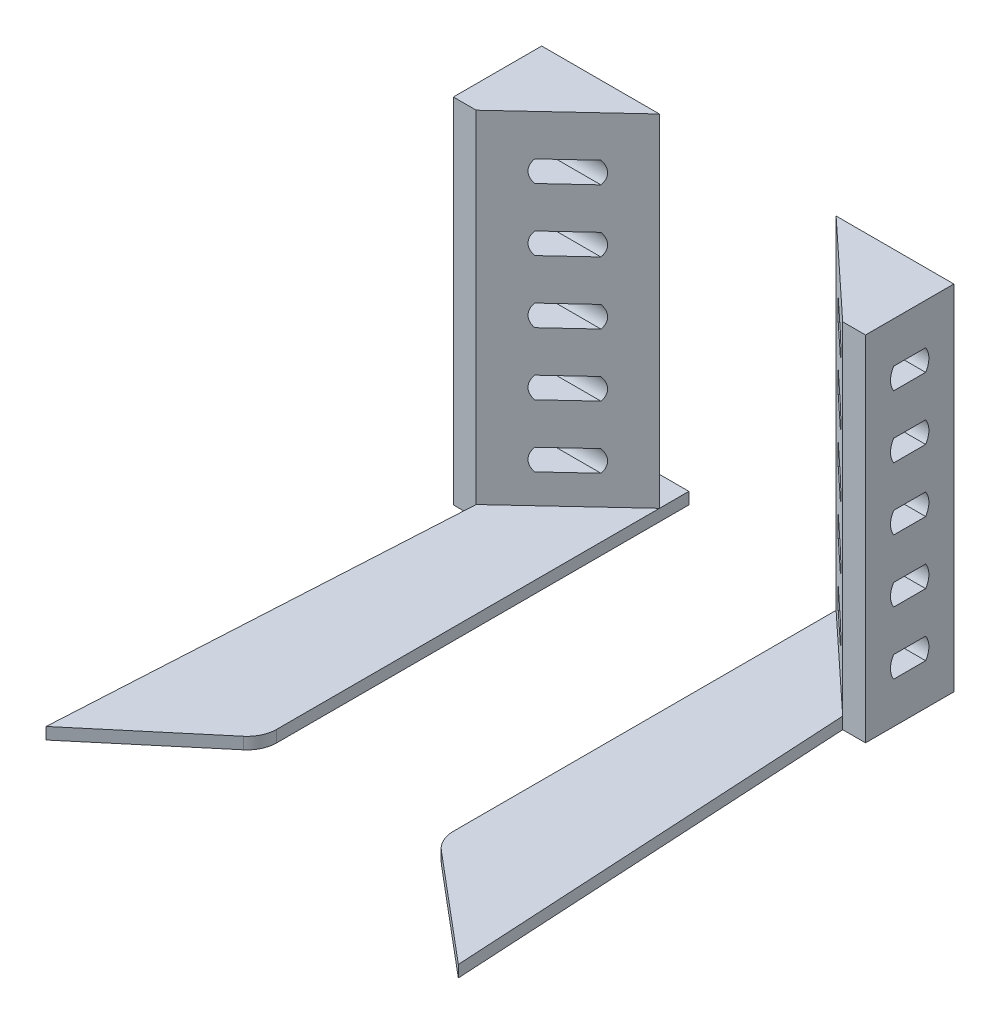
SolidWorks part; units mm, degrees
ref_plane "Front Plane" through (0, 0, 0) normal (0, 0, 1) x (1, 0, 0)
ref_plane "Top Plane" through (0, 0, 0) normal (0, 1, 0) x (1, 0, 0)
ref_plane "Right Plane" through (0, 0, 0) normal (1, 0, 0) x (0, 0, -1)
sketch "Sketch1" plane through (0, 0, 0) normal (0, 1, 0) x (1, 0, 0)
  line L0 (0, 0) -> (0, 13.4699) construction
  line L1 (0, 0) -> (3.6856, 0) construction
  line L2 (1.7808, -38.8258) -> (20, -54.1561)
  line L3 (0, 35) -> (15, 35)
  line L4 (0, 35) -> (0, -35)
  line L7 (15, 35) -> (20, -54.1561)
  line L8 (20, -54.1561) -> (20, 20.5292) construction
  line L9 (0, 30) -> (16.1216, 15)
  line L10 (20, 30) -> (0, 30)
  line L11 (20, 30) -> (20, 15)
  line L14 (16.1216, 15) -> (20, 15)
  line L15 (-15, 0) -> (-15, 85.0189) construction
  line L17 (-50, -54.1561) -> (-50, 20.5292) construction
  line L18 (-30, 0) -> (-33.6856, 0) construction
  line L19 (-30, 0) -> (-30, 13.4699) construction
  line L20 (-46.1216, 15) -> (-50, 15)
  line L21 (-50, 30) -> (-50, 15)
  line L22 (-50, 30) -> (-30, 30)
  line L23 (-30, 30) -> (-46.1216, 15)
  line L24 (-45, 35) -> (-50, -54.1561)
  line L25 (-30, 35) -> (-30, -35)
  line L26 (-30, 35) -> (-45, 35)
  line L27 (-31.7808, -38.8258) -> (-50, -54.1561)
  arc A0 (0, -35) -> (1.7808, -38.8258) centre (5, -35) ccw
  arc A1 (-30, -35) -> (-31.7808, -38.8258) centre (-35, -35) cw
  point P2 (0, 0)
  point P40 (0, 0)
  dimension "D1" = 5
  dimension "D2" = 20
  dimension "D3" = 15
  dimension "D4" = 70
  dimension "D5" = 46.712
  dimension "D6" = 15
  dimension "D7" = 5
  dimension "D8" = 15
extrude "Boss-Extrude1" add sketch "Sketch1" along normal blind 2 contours L10 L7 L3 L4 | L7 L10 L4 | L4 A0 L2 L7 | L11 L10 L7 region at (9.035, 0, 12.8099) region at (10.4673, 0, -25) region at (17.8437, 0, -22.7446) region at (7.5703, 0, -32.4923)
extrude "Boss-Extrude3" add sketch "Sketch1<5>" along normal blind 60 contours L7 L10 L9 | L7 L14 L11 L10 region at (10.4673, 0, -25) region at (17.8437, 0, -22.7446)
sketch "Sketch1<5>" plane through (0, 0, 0) normal (0, 1, 0) x (1, 0, 0) same geometry as "Sketch1"
sketch "Sketch4" plane through (20, 0, 0) normal (1, 0, 0) x (0, 0, -1)
  line L0 (30, 60) -> (15, 60) construction
  line L1 (19.79, 53.0167) -> (25.21, 53.0167)
  line L2 (19.2411, 51.2067) -> (25.7589, 51.2067) construction
  line L3 (19.79, 49.3967) -> (25.21, 49.3967)
  line L4 (22.5, 53.0167) -> (22.5, 49.3967) construction
  line L6 (19.79, 42.4133) -> (25.21, 42.4133)
  line L7 (19.2411, 40.6033) -> (25.7589, 40.6033) construction
  line L8 (19.79, 38.7933) -> (25.21, 38.7933)
  line L9 (22.5, 42.4133) -> (22.5, 38.7933) construction
  line L10 (19.79, 31.81) -> (25.21, 31.81)
  line L11 (19.2411, 30) -> (25.7589, 30) construction
  line L12 (19.79, 28.19) -> (25.21, 28.19)
  line L13 (22.5, 31.81) -> (22.5, 28.19) construction
  line L14 (19.79, 21.2067) -> (25.21, 21.2067)
  line L15 (19.2411, 19.3967) -> (25.7589, 19.3967) construction
  line L16 (19.79, 17.5867) -> (25.21, 17.5867)
  line L17 (22.5, 21.2067) -> (22.5, 17.5867) construction
  line L18 (19.79, 10.6033) -> (25.21, 10.6033)
  line L19 (19.2411, 8.7933) -> (25.7589, 8.7933) construction
  line L20 (19.79, 6.9833) -> (25.21, 6.9833)
  line L21 (22.5, 10.6033) -> (22.5, 6.9833) construction
  line L22 (22.5, 60) -> (22.5, 53.0167) construction
  line L23 (22.5, 49.3967) -> (22.5, 42.4133) construction
  line L24 (22.5, 38.7933) -> (22.5, 31.81) construction
  line L25 (22.5, 28.19) -> (22.5, 21.2067) construction
  line L26 (22.5, 17.5867) -> (22.5, 10.6033) construction
  line L27 (22.5, 6.9833) -> (22.5, 0) construction
  line L28 (30, 0) -> (15, 0) construction
  circle A0 centre (22.5, 51.2067) radius 3.2589 construction
  arc A1 (19.79, 53.0167) -> (19.79, 49.3967) centre (22.5, 51.2067) ccw
  arc A2 (25.21, 53.0167) -> (25.21, 49.3967) centre (22.5, 51.2067) cw
  circle A3 centre (22.5, 40.6033) radius 3.2589 construction
  arc A4 (19.79, 42.4133) -> (19.79, 38.7933) centre (22.5, 40.6033) ccw
  arc A5 (25.21, 42.4133) -> (25.21, 38.7933) centre (22.5, 40.6033) cw
  circle A6 centre (22.5, 30) radius 3.2589 construction
  arc A7 (19.79, 31.81) -> (19.79, 28.19) centre (22.5, 30) ccw
  arc A8 (25.21, 31.81) -> (25.21, 28.19) centre (22.5, 30) cw
  circle A9 centre (22.5, 19.3967) radius 3.2589 construction
  arc A10 (19.79, 21.2067) -> (19.79, 17.5867) centre (22.5, 19.3967) ccw
  arc A11 (25.21, 21.2067) -> (25.21, 17.5867) centre (22.5, 19.3967) cw
  circle A12 centre (22.5, 8.7933) radius 3.2589 construction
  arc A13 (19.79, 10.6033) -> (19.79, 6.9833) centre (22.5, 8.7933) ccw
  arc A14 (25.21, 10.6033) -> (25.21, 6.9833) centre (22.5, 8.7933) cw
  point P4 (22.5, 60)
  dimension "D1" = 5.42
  dimension "D2" = 3.62
extrude "Cut-Extrude1" cut sketch "Sketch4" against normal through all both and the other way through all
extrude "Boss-Extrude5" add sketch "Sketch1<9>" along normal blind 2 separate body contours A1 L25 L23 L24 L27 | L24 L22 L21 L20 | L22 L24 L23 | L25 L26 L24 L22 region at (-40.4673, 0, -25) region at (-39.035, 0, 12.8099) region at (-47.8437, 0, -22.7446) region at (-37.5703, 0, -32.4923)
sketch "Sketch1<9>" plane through (0, 0, 0) normal (0, 1, 0) x (1, 0, 0) same geometry as "Sketch1"
extrude "Boss-Extrude6" add sketch "Sketch1<10>" along normal blind 60 contours L22 L24 L23 | L24 L22 L21 L20 region at (-40.4673, 0, -25) region at (-47.8437, 0, -22.7446)
sketch "Sketch1<10>" plane through (0, 0, 0) normal (0, 1, 0) x (1, 0, 0) same geometry as "Sketch1"
sketch "Sketch7" plane through (-50, 0, 0) normal (-1, 0, 0) x (0, 0, 1)
  line L0 (-25.21, 53.0167) -> (-19.79, 53.0167)
  line L1 (-25.7589, 51.2067) -> (-19.2411, 51.2067) construction
  line L2 (-25.21, 49.3967) -> (-19.79, 49.3967)
  line L3 (-22.5, 53.0167) -> (-22.5, 49.3967) construction
  line L4 (-25.21, 42.4133) -> (-19.79, 42.4133)
  line L5 (-25.7589, 40.6033) -> (-19.2411, 40.6033) construction
  line L6 (-25.21, 38.7933) -> (-19.79, 38.7933)
  line L7 (-22.5, 42.4133) -> (-22.5, 38.7933) construction
  line L8 (-25.21, 31.81) -> (-19.79, 31.81)
  line L9 (-25.7589, 30) -> (-19.2411, 30) construction
  line L10 (-25.21, 28.19) -> (-19.79, 28.19)
  line L11 (-22.5, 31.81) -> (-22.5, 28.19) construction
  line L12 (-25.21, 21.2067) -> (-19.79, 21.2067)
  line L13 (-25.7589, 19.3967) -> (-19.2411, 19.3967) construction
  line L14 (-25.21, 17.5867) -> (-19.79, 17.5867)
  line L15 (-22.5, 21.2067) -> (-22.5, 17.5867) construction
  line L16 (-25.21, 10.6033) -> (-19.79, 10.6033)
  line L17 (-25.7589, 8.7933) -> (-19.2411, 8.7933) construction
  line L18 (-25.21, 6.9833) -> (-19.79, 6.9833)
  line L19 (-22.5, 10.6033) -> (-22.5, 6.9833) construction
  line L20 (-22.5, 60) -> (-22.5, 53.0167) construction
  line L21 (-22.5, 49.3967) -> (-22.5, 42.4133) construction
  line L22 (-22.5, 38.7933) -> (-22.5, 31.81) construction
  line L23 (-22.5, 28.19) -> (-22.5, 21.2067) construction
  line L24 (-22.5, 17.5867) -> (-22.5, 10.6033) construction
  line L25 (-22.5, 6.9833) -> (-22.5, 0) construction
  line L26 (-30, 0) -> (-15, 0) construction
  line L27 (-30, 60) -> (-15, 60) construction
  circle A0 centre (-22.5, 51.2067) radius 3.2589 construction
  arc A1 (-25.21, 53.0167) -> (-25.21, 49.3967) centre (-22.5, 51.2067) ccw
  arc A2 (-19.79, 53.0167) -> (-19.79, 49.3967) centre (-22.5, 51.2067) cw
  circle A3 centre (-22.5, 40.6033) radius 3.2589 construction
  arc A4 (-25.21, 42.4133) -> (-25.21, 38.7933) centre (-22.5, 40.6033) ccw
  arc A5 (-19.79, 42.4133) -> (-19.79, 38.7933) centre (-22.5, 40.6033) cw
  circle A6 centre (-22.5, 30) radius 3.2589 construction
  arc A7 (-25.21, 31.81) -> (-25.21, 28.19) centre (-22.5, 30) ccw
  arc A8 (-19.79, 31.81) -> (-19.79, 28.19) centre (-22.5, 30) cw
  circle A9 centre (-22.5, 19.3967) radius 3.2589 construction
  arc A10 (-25.21, 21.2067) -> (-25.21, 17.5867) centre (-22.5, 19.3967) ccw
  arc A11 (-19.79, 21.2067) -> (-19.79, 17.5867) centre (-22.5, 19.3967) cw
  circle A12 centre (-22.5, 8.7933) radius 3.2589 construction
  arc A13 (-25.21, 10.6033) -> (-25.21, 6.9833) centre (-22.5, 8.7933) ccw
  arc A14 (-19.79, 10.6033) -> (-19.79, 6.9833) centre (-22.5, 8.7933) cw
  point P52 (0, 0)
  point P55 (-22.5, 0)
  point P56 (0, 0)
  point P59 (-22.5, 60)
  dimension "D1" = 5.42
  dimension "D2" = 3.62
extrude "Cut-Extrude2" cut sketch "Sketch7" against normal through all both and the other way through all
